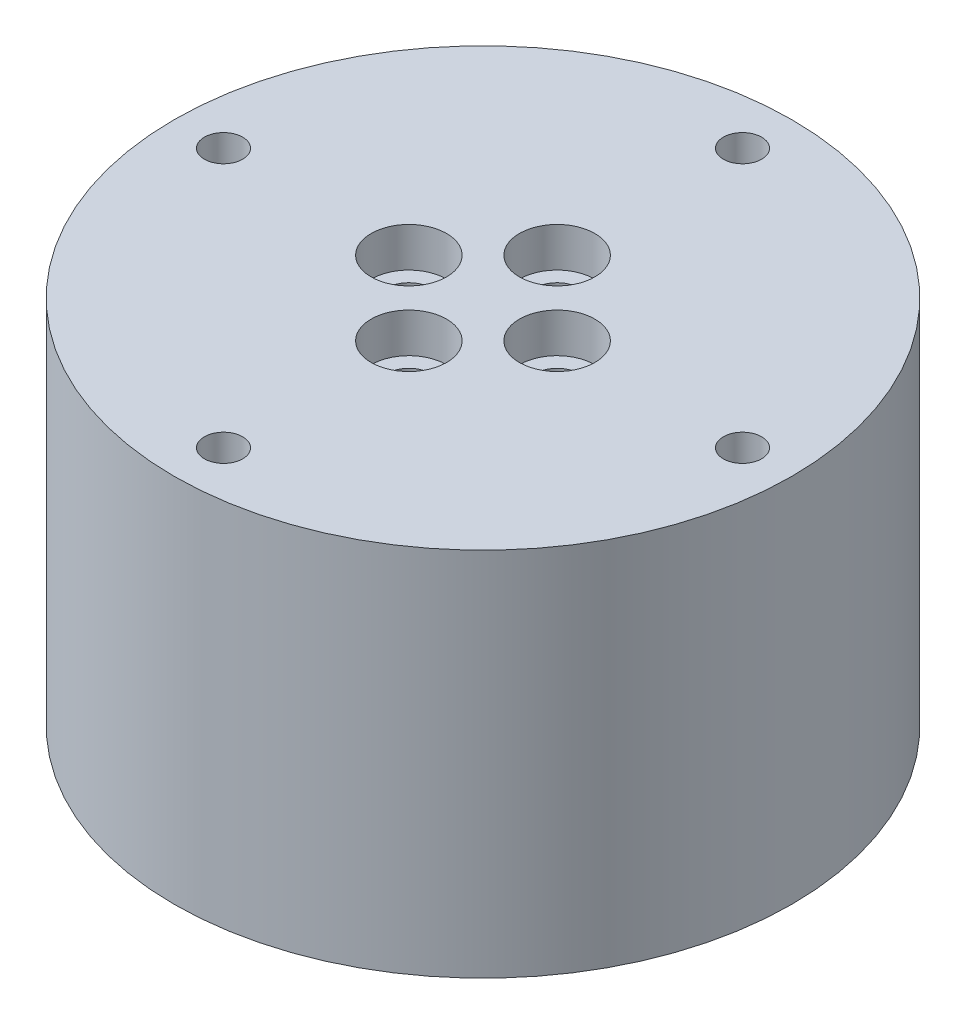
SolidWorks part; units mm, degrees
ref_plane "Front Plane" through (0, 0, 0) normal (0, 0, 1) x (1, 0, 0)
ref_plane "Top Plane" through (0, 0, 0) normal (0, 1, 0) x (1, 0, 0)
ref_plane "Right Plane" through (0, 0, 0) normal (1, 0, 0) x (0, 0, -1)
sketch "Sketch1" plane through (0, 0, 0) normal (0, 1, 0) x (1, 0, 0)
  circle A0 centre (0, 0) radius 25
  dimension "D1" = 50
extrude "Boss-Extrude1" add sketch "Sketch1" against normal blind 5
sketch "Sketch2" plane through (0, -5, 0) normal (0, -1, 0) x (1, 0, 0)
  circle A0 centre (0, 0) radius 25
  circle A1 centre (0, 0) radius 15.5
  circle A2 centre (0, 0) radius 25 construction
  dimension "D1" = 31
extrude "Boss-Extrude2" add sketch "Sketch2" along normal blind 25
sketch "Sketch3" plane through (0, 0, 0) normal (0, 1, 0) x (1, 0, 0)
  circle A0 centre (0, 0) radius 6 construction
  circle A1 centre (0, 6) radius 1.8
  circle A2 centre (0, 6) radius 3.05
  dimension "D1" = 12
  dimension "D2" = 3.6
  dimension "D3" = 6.1
extrude "Cut-Extrude1" cut sketch "Sketch3" against normal blind 3.2
extrude "Cut-Extrude2" cut sketch "Sketch3<2>" against normal up to next contours A1 region at (0, 0, -6)
sketch "Sketch3<2>" plane through (0, 0, 0) normal (0, 1, 0) x (1, 0, 0) same geometry as "Sketch3"
sketch "Sketch4" plane through (0, 0, 0) normal (0, 1, 0) x (1, 0, 0)
  circle A0 centre (0, 21) radius 1.55
  dimension "D1" = 3.1
  dimension "D3" = 21
extrude "Cut-Extrude4" cut sketch "Sketch4" against normal blind 7 contours A0 region at (0, 0, -21)
pattern_circular "CirPattern1" count 4 over 360 about axis through (0, -5, 0) along (0, 1, 0) of "Cut-Extrude1", "Cut-Extrude2", "Cut-Extrude4" reverse direction yes
fillet "Fillet1" radius 9 1 edges at (0, -30, -15.5)
fillet "Fillet2" radius 2 1 edges at (0, -5, -15.5)
